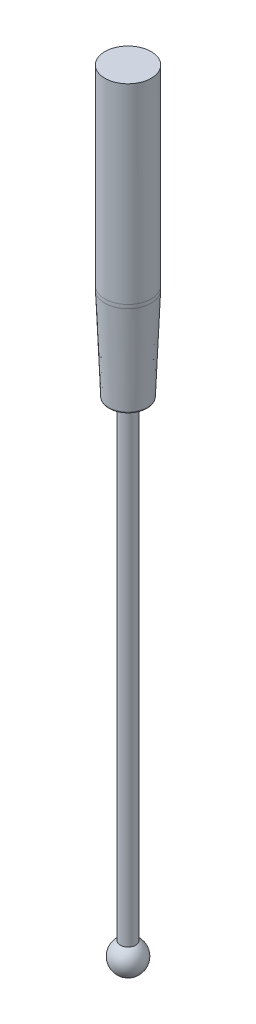
SolidWorks part; units mm, degrees
ref_plane "Front Plane" through (0, 0, 0) normal (0, 0, 1) x (1, 0, 0)
ref_plane "Top Plane" through (0, 0, 0) normal (0, 1, 0) x (1, 0, 0)
ref_plane "Right Plane" through (0, 0, 0) normal (1, 0, 0) x (0, 0, -1)
sketch "Sketch1" plane through (0, 0, 0) normal (0, 0, 1) x (1, 0, 0)
  line L0 (0, -1574.8918) -> (0, 77169.6981) construction
  line L1 (0, 0) -> (1.5, 0)
  line L2 (1.5, 0) -> (1.5, -12.5)
  line L3 (1.5, -12.5) -> (1.25, -18.682)
  line L4 (0.5, -18.682) -> (0.5, -49.134)
  line L5 (1.25, -18.682) -> (0.5, -18.682)
  line L6 (0, -51) -> (0, 0)
  arc A0 (0, -51) -> (0.5, -49.134) centre (0, -50) ccw
  point P7 (1.25, -14.8075)
  point P10 (1.5, -18.682)
  dimension "D1" = 2
  dimension "D4" = 1
  dimension "D2" = 3
  dimension "D3" = 50
  dimension "D5" = 2.5
  dimension "D6" = 177.684
  dimension "D7" = 12.5
revolve "Revolve1" add sketch "Sketch1" angle 360 about L0
fillet "Fillet1" radius 0.1 1 edges at (1.25, -18.682, 0)
fillet "Fillet2" radius 6 1 edges at (1.5, -12.5, 0)
